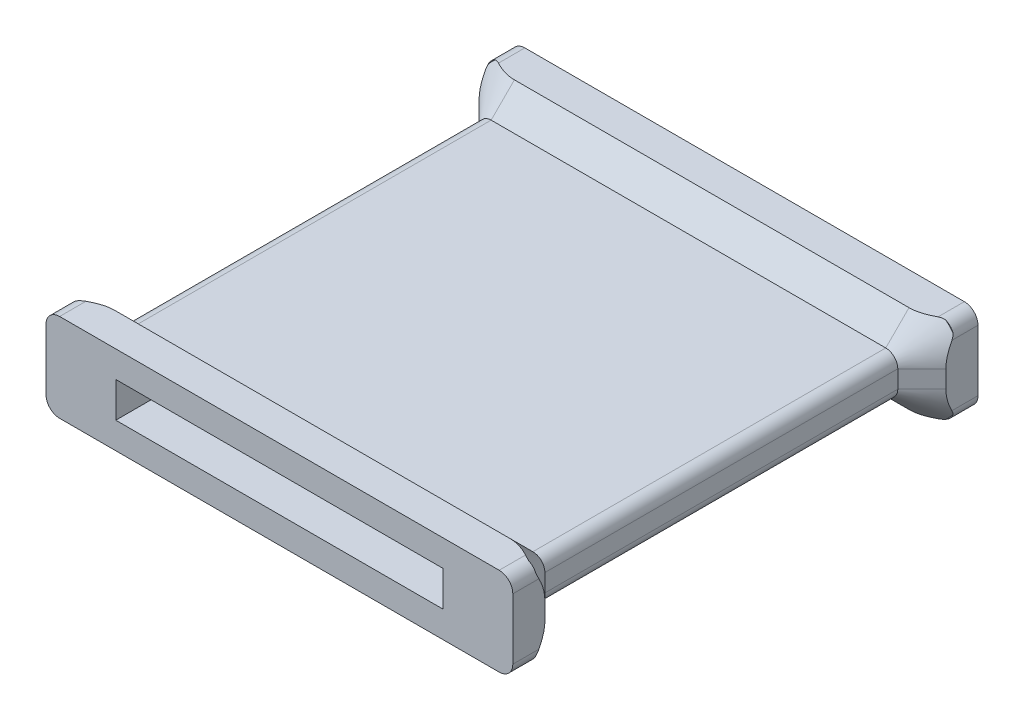
SolidWorks part; units mm, degrees
ref_plane "Front Plane" through (0, 0, 0) normal (0, 0, 1) x (1, 0, 0)
ref_plane "Top Plane" through (0, 0, 0) normal (0, 1, 0) x (1, 0, 0)
ref_plane "Right Plane" through (0, 0, 0) normal (1, 0, 0) x (0, 0, -1)
sketch "Sketch1" plane through (0, 0, 0) normal (0, 0, 1) x (1, 0, 0)
  line L1 (-20.4, 2.2) -> (20.4, 2.2)
  line L2 (-20.4, 2.2) -> (-20.4, -2.2)
  line L3 (-20.4, -2.2) -> (20.4, -2.2)
  line L4 (20.4, 2.2) -> (20.4, -2.2)
  line L5 (-20.4, 2.2) -> (20.4, -2.2) construction
  line L6 (-20.4, -2.2) -> (20.4, 2.2) construction
  line L7 (-29.1, 5.5) -> (29.1, 5.5)
  line L8 (-29.1, 5.5) -> (-29.1, -5.5)
  line L9 (-29.1, -5.5) -> (29.1, -5.5)
  line L10 (29.1, 5.5) -> (29.1, -5.5)
  line L11 (-29.1, 5.5) -> (29.1, -5.5) construction
  line L12 (-29.1, -5.5) -> (29.1, 5.5) construction
  point P0 (0, 0)
  point P6 (0, 0)
  dimension "D1" = 40.8
  dimension "D2" = 4.4
  dimension "D3" = 11
  dimension "D4" = 58.2
extrude "Boss-Extrude1" add sketch "Sketch1" along normal blind 58
sketch "Sketch2" plane through (0, 0, 58) normal (0, 0, 1) x (1, 0, 0)
  line L0 (20.4, 2.2) -> (-20.4, 2.2) construction
  line L1 (-26.1, 2.6) -> (26.1, 2.6)
  line L2 (-26.1, 2.6) -> (-26.1, -2.6)
  line L3 (-26.1, -2.6) -> (26.1, -2.6)
  line L4 (26.1, 2.6) -> (26.1, -2.6)
  line L5 (-26.1, 2.6) -> (26.1, -2.6) construction
  line L6 (-26.1, -2.6) -> (26.1, 2.6) construction
  line L7 (-29.1, 5.5) -> (-29.1, -5.5) construction
  point P0 (0, 0)
  dimension "D1" = 0.4
  dimension "D2" = 3
extrude "Cut-Extrude1" cut sketch "Sketch2" against normal offset from surface (52 mm away) 3 from offset 3 flip side to cut up to face at (0, 0, 0) offset against normal yes
fillet "Fillet1" radius 1.5 4 edges at (26.1, -2.6, 29) (26.1, 2.6, 29) (-26.1, -2.6, 29) (-26.1, 2.6, 29)
fillet "Fillet2" radius 1.7 8 edges at (29.1, -5.5, 1.5) (29.1, 5.5, 1.5) (29.1, -5.5, 56.5) (29.1, 5.5, 56.5) (-29.1, -5.5, 56.5) (-29.1, 5.5, 56.5) (-29.1, -5.5, 1.5) (-29.1, 5.5, 1.5)
chamfer "Chamfer1" distance 4 angle 45 16 edges at (0, -2.6, 3) (-25.6607, -2.1607, 3) (25.6607, -2.1607, 3) (-26.1, 0, 3) (26.1, 0, 3) (-25.6607, 2.1607, 3) (25.6607, 2.1607, 3) (0, 2.6, 3) (0, -2.6, 55) (25.6607, -2.1607, 55) (-25.6607, -2.1607, 55) (26.1, 0, 55) (-26.1, 0, 55) (25.6607, 2.1607, 55) (-25.6607, 2.1607, 55) (0, 2.6, 55)
